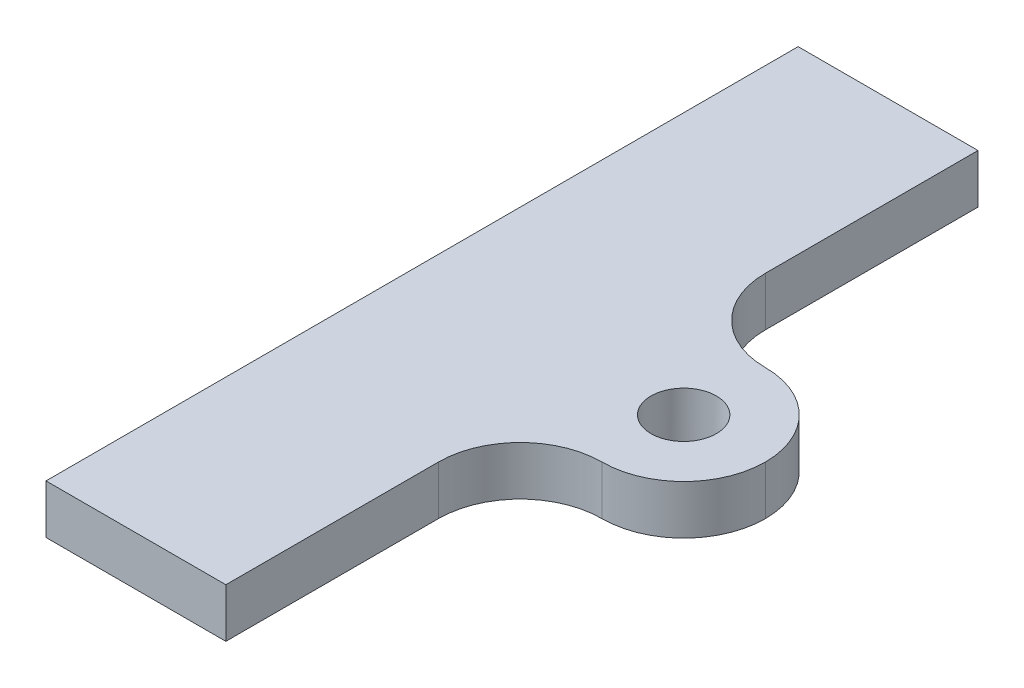
SolidWorks part; units mm, degrees
ref_plane "Front Plane" through (0, 0, 0) normal (0, 0, 1) x (1, 0, 0)
ref_plane "Top Plane" through (0, 0, 0) normal (0, 1, 0) x (1, 0, 0)
ref_plane "Right Plane" through (0, 0, 0) normal (1, 0, 0) x (0, 0, -1)
sketch "Sketch1" plane through (0, 0, 0) normal (0, 1, 0) x (1, 0, 0)
  line L1 (-4.5, -23) -> (4.5, -23)
  line L2 (-4.5, -23) -> (-4.5, 23)
  line L3 (-4.5, 23) -> (4.5, 23)
  line L4 (4.5, -23) -> (4.5, 23)
  line L5 (-4.5, -23) -> (4.5, 23) construction
  line L6 (-4.5, 23) -> (4.5, -23) construction
  point P0 (0, 0)
  dimension "D1" = 46
  dimension "D2" = 9
extrude "Boss-Extrude1" add sketch "Sketch1" along normal blind 3
sketch "Sketch2" plane through (0, 3, 0) normal (0, 1, 0) x (1, 0, 0)
  line L0 (4.5, 0) -> (-1.7, 0) construction
  line L1 (4.5, -23) -> (4.5, 23) construction
  line L2 (-1.7, 0) -> (-1.7, -9) construction
  line L3 (-1.7, 0) -> (-1.7, 6) construction
  circle A0 centre (-1.7, -9) radius 1.25
  circle A1 centre (-1.7, 6) radius 1.25
  dimension "D4" = 2.5
  dimension "D1" = 6.2
  dimension "D2" = 9
  dimension "D3" = 6
extrude "Boss-Extrude2" add sketch "Sketch2" against normal blind 5
sketch "Sketch3" plane through (4.5, 0, 0) normal (1, 0, 0) x (0, 0, -1)
  line L12 (-23, 0) -> (23, 0)
  line L13 (23, 0) -> (23, 3)
  line L14 (23, 3) -> (-23, 3)
  line L15 (-23, 3) -> (-23, 0)
  line L16 (-23, 0) -> (23, 0)
  line L17 (23, 0) -> (23, 3)
  line L18 (23, 3) -> (-23, 3)
  line L19 (-23, 3) -> (-23, 0)
  dimension "D1" = 0
extrude "Boss-Extrude3" add sketch "Sketch3" along normal blind 2
sketch "Sketch4" plane through (6.5, 0, 0) normal (1, 0, 0) x (0, 0, -1)
  line L0 (0, 0) -> (0, 3) construction
  line L1 (23, 3) -> (-23, 3) construction
  line L3 (-5, 0) -> (5, 0)
  line L4 (-5, 0) -> (-5, 3)
  line L5 (-5, 3) -> (5, 3)
  line L6 (5, 0) -> (5, 3)
  line L7 (-5, 0) -> (5, 3) construction
  line L8 (-5, 3) -> (5, 0) construction
  point P5 (0, 1.5)
  dimension "D1" = 10
extrude "Boss-Extrude4" add sketch "Sketch4" along normal blind 10
sketch "Sketch5" plane through (0, 3, 0) normal (0, 1, 0) x (1, 0, 0)
  line L0 (6.5, 5) -> (6.5, -5) construction
  line L1 (6.5, 0) -> (16.5, 0) construction
  line L2 (16.5, 5) -> (16.5, -5) construction
  circle A0 centre (11.5, 0) radius 2
  dimension "D1" = 4
extrude "Cut-Extrude1" cut sketch "Sketch5" against normal blind 10
fillet "Fillet1" radius 5 2 edges at (16.5, 1.5, 5) (16.5, 1.5, -5)
fillet "Fillet2" radius 5 2 edges at (6.5, 1.5, -5) (6.5, 1.5, 5)
